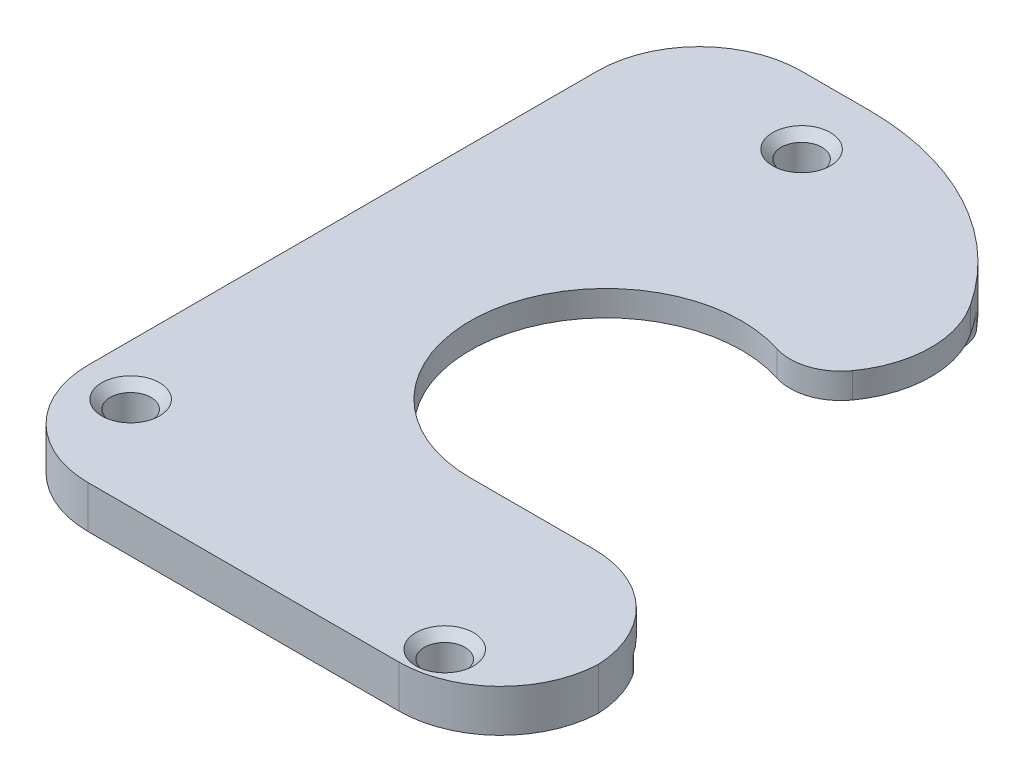
SolidWorks part; units mm, degrees
ref_plane "Plan de face" through (0, 0, 0) normal (0, 0, 1) x (1, 0, 0)
ref_plane "Plan de dessus" through (0, 0, 0) normal (0, 1, 0) x (1, 0, 0)
ref_plane "Plan de droite" through (0, 0, 0) normal (1, 0, 0) x (0, 0, -1)
sketch "Esquisse1" plane through (0, 0, 0) normal (0, 1, 0) x (1, 0, 0)
  line L0 (-17, 22.5) -> (-17, -19.5)
  line L1 (-17, -19.5) -> (13.3, -19.5)
  line L2 (-17, 22.5) -> (-7, 22.5)
  line L5 (0, -8) -> (13.3, -8)
  line L6 (13.3, -8) -> (13.3, -19.5)
  line L7 (3.873, 7) -> (8.4853, 7)
  arc A0 (3.873, 7) -> (0, -8) centre (0, 0) ccw
  arc A1 (8.4853, 7) -> (-7, 22.5) centre (-7, 7.0147) ccw
  point P1 (-2.6574, 3.0009)
  point P13 (0, 0)
  dimension "D1" = 16
  dimension "D2" = 13.3
  dimension "D3" = 17
  dimension "D4" = 22.5
  dimension "D5" = 19.5
  dimension "D6" = 11
  dimension "D7" = 15
  dimension "D8" = 10
extrude "Boss.-Extru.1" add sketch "Esquisse1" along normal blind 2.5
sketch "Esquisse2" plane through (0, 2.5, 0) normal (0, 1, 0) x (1, 0, 0)
  circle A0 centre (-14, -14) radius 1.2
  circle A1 centre (-7, 18.5213) radius 1.2
  circle A2 centre (8, -17.5) radius 1.2
  dimension "D7" = 2.4
  dimension "D1" = 14
  dimension "D2" = 14
  dimension "D3" = 8
  dimension "D4" = 17.5
  dimension "D5" = 19.8
  dimension "D6" = 7
extrude "Enlèv. mat.-Extru.1" cut sketch "Esquisse2" against normal through all
fillet "Congé1" radius 6 5 edges at (-17, 1.25, -22.5) (-17, 1.25, 19.5) (8.4853, 1.25, -7) (13.3, 1.25, 8) (13.3, 1.25, 19.5) tangent propagation no
fillet "Congé3" radius 3 1 edges at (3.873, 1.25, -7)
sketch "Esquisse4" plane through (0, 0, 0) normal (0, -1, 0) x (1, 0, 0)
  circle A0 centre (0, 0) radius 14
  dimension "D1" = 28
extrude "Enlèv. mat.-Extru.2" cut sketch "Esquisse4" against normal blind 1
fillet "Congé5" radius 2 2 edges at (10.685, 0.5, 9.046) (6.9251, 0.5, -12.1673)
chamfer "Chanfrein1" distance 0.5 angle 45 3 edges at (8, 2.5, 18.7) (-14, 2.5, 15.2) (-7, 2.5, -17.3213)
